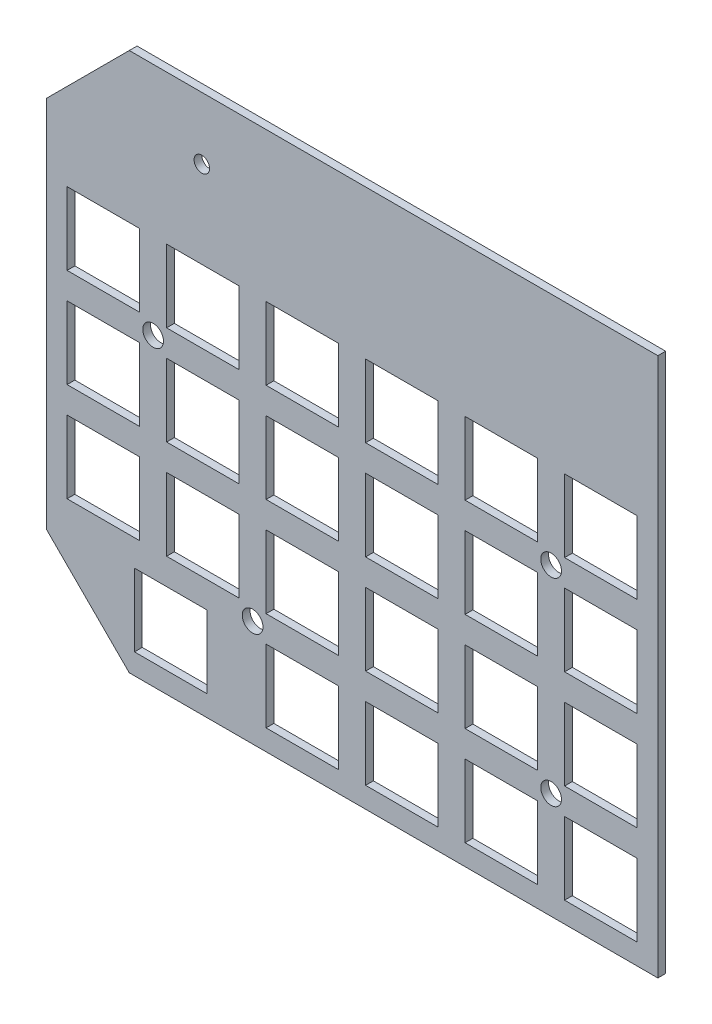
SolidWorks part; units mm, degrees
ref_plane "Plan de face" through (0, 0, 0) normal (0, 0, 1) x (1, 0, 0)
ref_plane "Plan de dessus" through (0, 0, 0) normal (0, 1, 0) x (1, 0, 0)
ref_plane "Plan de droite" through (0, 0, 0) normal (1, 0, 0) x (0, 0, -1)
sketch "Esquisse1" plane through (0, 0, 0) normal (0, 0, 1) x (1, 0, 0)
  line L0 (0, -85) -> (16, -101)
  line L4 (118, 3) -> (118, -101)
  line L5 (16, 3) -> (0, -13)
  line L7 (118, 3) -> (16, 3)
  line L8 (0, -13) -> (0, -85)
  line L9 (16, -101) -> (118, -101)
  dimension "D1" = 104
  dimension "D2" = 118
  dimension "D3" = 16
  dimension "D4" = 16
  dimension "D5" = 16
  dimension "D6" = 16
extrude "Boss.-Extru.1" add sketch "Esquisse1" along normal blind 1.5
sketch "Esquisse2" plane through (0, 0, 1.5) normal (0, 0, 1) x (1, 0, 0)
  line L0 (0, -13) -> (0, -85) construction
  line L1 (4, -25.7494) -> (18, -25.7494)
  line L2 (4, -25.7494) -> (4, -39.7494)
  line L3 (4, -39.7494) -> (18, -39.7494)
  line L4 (18, -25.7494) -> (18, -39.7494)
  line L5 (11, -39.7494) -> (11, -25.7494) construction
  line L6 (4, -32.7494) -> (18, -32.7494) construction
  line L7 (118, 3) -> (16, 3) construction
  line L12 (23.2, -25.7494) -> (23.2, -39.7494)
  line L13 (23.2, -25.7494) -> (37.2, -25.7494)
  line L14 (37.2, -25.7494) -> (37.2, -39.7494)
  line L15 (23.2, -39.7494) -> (37.2, -39.7494)
  line L16 (42.4, -25.7494) -> (42.4, -39.7494)
  line L17 (42.4, -25.7494) -> (56.4, -25.7494)
  line L18 (56.4, -25.7494) -> (56.4, -39.7494)
  line L19 (42.4, -39.7494) -> (56.4, -39.7494)
  line L20 (61.6, -25.7494) -> (61.6, -39.7494)
  line L21 (61.6, -25.7494) -> (75.6, -25.7494)
  line L22 (75.6, -25.7494) -> (75.6, -39.7494)
  line L23 (61.6, -39.7494) -> (75.6, -39.7494)
  line L24 (80.8, -25.7494) -> (80.8, -39.7494)
  line L25 (80.8, -25.7494) -> (94.8, -25.7494)
  line L26 (94.8, -25.7494) -> (94.8, -39.7494)
  line L27 (80.8, -39.7494) -> (94.8, -39.7494)
  line L28 (100, -25.7494) -> (100, -39.7494)
  line L29 (100, -25.7494) -> (114, -25.7494)
  line L30 (114, -25.7494) -> (114, -39.7494)
  line L31 (100, -39.7494) -> (114, -39.7494)
  line L32 (23.2, -44.8329) -> (23.2, -58.8329)
  line L33 (23.2, -44.8329) -> (37.2, -44.8329)
  line L34 (37.2, -44.8329) -> (37.2, -58.8329)
  line L35 (23.2, -58.8329) -> (37.2, -58.8329)
  line L36 (42.4, -44.8329) -> (42.4, -58.8329)
  line L37 (42.4, -44.8329) -> (56.4, -44.8329)
  line L38 (56.4, -44.8329) -> (56.4, -58.8329)
  line L39 (42.4, -58.8329) -> (56.4, -58.8329)
  line L40 (61.6, -44.8329) -> (61.6, -58.8329)
  line L41 (61.6, -44.8329) -> (75.6, -44.8329)
  line L42 (75.6, -44.8329) -> (75.6, -58.8329)
  line L43 (61.6, -58.8329) -> (75.6, -58.8329)
  line L44 (80.8, -44.8329) -> (80.8, -58.8329)
  line L45 (80.8, -44.8329) -> (94.8, -44.8329)
  line L46 (94.8, -44.8329) -> (94.8, -58.8329)
  line L47 (80.8, -58.8329) -> (94.8, -58.8329)
  line L48 (100, -44.8329) -> (100, -58.8329)
  line L49 (100, -44.8329) -> (114, -44.8329)
  line L50 (114, -44.8329) -> (114, -58.8329)
  line L51 (100, -58.8329) -> (114, -58.8329)
  line L52 (23.2, -63.9165) -> (23.2, -77.9165)
  line L53 (23.2, -63.9165) -> (37.2, -63.9165)
  line L54 (37.2, -63.9165) -> (37.2, -77.9165)
  line L55 (23.2, -77.9165) -> (37.2, -77.9165)
  line L56 (42.4, -63.9165) -> (42.4, -77.9165)
  line L57 (42.4, -63.9165) -> (56.4, -63.9165)
  line L58 (56.4, -63.9165) -> (56.4, -77.9165)
  line L59 (42.4, -77.9165) -> (56.4, -77.9165)
  line L60 (61.6, -63.9165) -> (61.6, -77.9165)
  line L61 (61.6, -63.9165) -> (75.6, -63.9165)
  line L62 (75.6, -63.9165) -> (75.6, -77.9165)
  line L63 (61.6, -77.9165) -> (75.6, -77.9165)
  line L64 (80.8, -63.9165) -> (80.8, -77.9165)
  line L65 (80.8, -63.9165) -> (94.8, -63.9165)
  line L66 (94.8, -63.9165) -> (94.8, -77.9165)
  line L67 (80.8, -77.9165) -> (94.8, -77.9165)
  line L68 (100, -63.9165) -> (100, -77.9165)
  line L69 (100, -63.9165) -> (114, -63.9165)
  line L70 (114, -63.9165) -> (114, -77.9165)
  line L71 (100, -77.9165) -> (114, -77.9165)
  line L72 (4, -44.8329) -> (4, -58.8329)
  line L73 (4, -44.8329) -> (18, -44.8329)
  line L74 (18, -44.8329) -> (18, -58.8329)
  line L75 (4, -58.8329) -> (18, -58.8329)
  line L76 (4, -63.9165) -> (4, -77.9165)
  line L77 (4, -63.9165) -> (18, -63.9165)
  line L78 (18, -63.9165) -> (18, -77.9165)
  line L79 (4, -77.9165) -> (18, -77.9165)
  line L112 (42.4, -83) -> (42.4, -97)
  line L113 (42.4, -83) -> (56.4, -83)
  line L114 (56.4, -83) -> (56.4, -97)
  line L115 (42.4, -97) -> (56.4, -97)
  line L116 (61.6, -83) -> (61.6, -97)
  line L117 (61.6, -83) -> (75.6, -83)
  line L118 (75.6, -83) -> (75.6, -97)
  line L119 (61.6, -97) -> (75.6, -97)
  line L120 (80.8, -83) -> (80.8, -97)
  line L121 (80.8, -83) -> (94.8, -83)
  line L122 (94.8, -83) -> (94.8, -97)
  line L123 (80.8, -97) -> (94.8, -97)
  line L124 (100, -83) -> (100, -97)
  line L125 (100, -83) -> (114, -83)
  line L126 (114, -83) -> (114, -97)
  line L127 (100, -97) -> (114, -97)
  line L128 (4, -83) -> (4, -97) [skipped]
  line L129 (4, -83) -> (18, -83) [skipped]
  line L130 (18, -83) -> (18, -97) [skipped]
  line L131 (4, -97) -> (18, -97) [skipped]
  line L132 (23.2, -83) -> (23.2, -97) [skipped]
  line L133 (23.2, -83) -> (37.2, -83) [skipped]
  line L134 (37.2, -83) -> (37.2, -97) [skipped]
  line L135 (23.2, -97) -> (37.2, -97) [skipped]
  line L137 (17, -83) -> (31, -83)
  line L138 (17, -83) -> (17, -97)
  line L139 (17, -97) -> (31, -97)
  line L140 (31, -83) -> (31, -97)
  line L141 (24, -97) -> (24, -83) construction
  line L142 (17, -90) -> (31, -90) construction
  line L143 (16, -101) -> (118, -101) construction
  line L144 (18, -39.7494) -> (23.2, -44.8329) construction
  line L146 (94.8, -39.7494) -> (100, -44.8329) construction
  line L147 (94.8, -77.9165) -> (100, -83) construction
  line L148 (37.2, -77.9165) -> (42.4, -83) construction
  circle A4 centre (20.6, -42.2911) radius 2
  circle A5 centre (97.4, -42.2911) radius 2
  circle A6 centre (97.4, -80.4582) radius 2
  circle A7 centre (39.8, -80.4582) radius 2
  circle A8 centre (30, -9) radius 1.5
  point P0 (11, -32.7494)
  point P19 (24, -90)
  dimension "D5" = 4
  dimension "D7" = 12
  dimension "D6" = 30
  dimension "D1" = 14
  dimension "D2" = 14
  dimension "D3" = 4
  dimension "D4" = 6
  dimension "D9" = 14
  dimension "D10" = 14
  dimension "D11" = 17
  dimension "D12" = 5.2
  dimension "D8" = 4
extrude "Enlèv. mat.-Extru.1" cut sketch "Esquisse2" against normal blind 1.5
